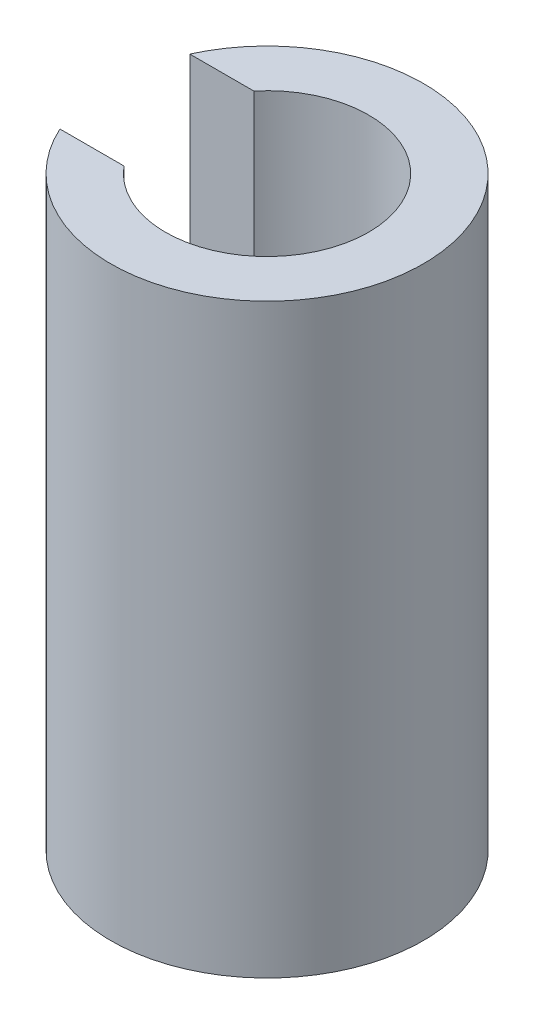
SolidWorks part; units mm, degrees
ref_plane "前基準面" through (0, 0, 0) normal (0, 0, 1) x (1, 0, 0)
ref_plane "上基準面" through (0, 0, 0) normal (0, 1, 0) x (1, 0, 0)
ref_plane "右基準面" through (0, 0, 0) normal (1, 0, 0) x (0, 0, -1)
ref_axis "基準軸1" through (0, -55, 0) along (0, 1, 0)
ref_axis "基準軸2" through (-88.99, 0, 0) along (1, 0, 0)
ref_axis "基準軸3" through (0, 0, 55) along (0, 0, -1)
sketch "草圖1" plane through (0, 0, 0) normal (0, 1, 0) x (1, 0, 0)
  circle A0 centre (0, 0) radius 2.6
  circle A1 centre (0, 0) radius 4
  dimension "D1" = 5.2
  dimension "D2" = 8
extrude "填料-伸長1" add sketch "草圖1" along normal blind 15
sketch "草圖2" plane through (0, 15, 0) normal (0, 1, 0) x (1, 0, 0)
  line L1 (-4, -1.6613) -> (-2, -1.6613)
  line L2 (-4, -1.6613) -> (-4, 1.6613)
  line L3 (-4, 1.6613) -> (-2, 1.6613)
  line L4 (-2, -1.6613) -> (-2, 1.6613)
  line L5 (-55, 0) -> (55, 0) construction
  circle A0 centre (0, 0) radius 4 construction
  circle A1 centre (0, 0) radius 2.6 construction
  point P4 (-2, 0)
  dimension "D1" = 2
extrude "除料-伸長1" cut sketch "草圖2" against normal blind 15
